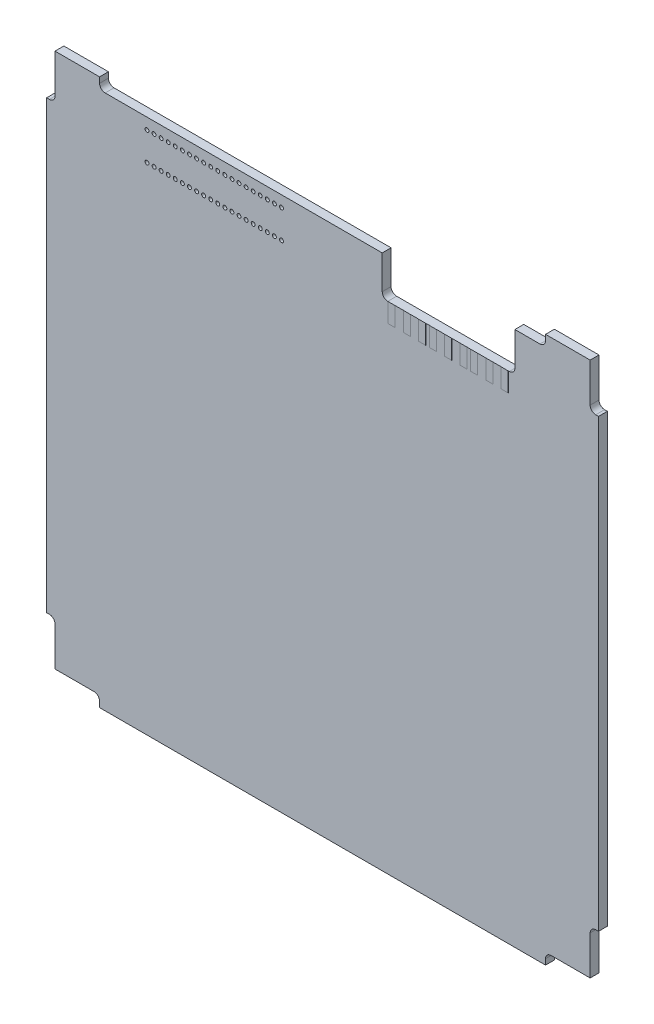
SolidWorks part; units mm, degrees
material "ABS"
ref_plane "Front Plane" through (0, 0, 0) normal (0, 0, 1) x (1, 0, 0)
ref_plane "Top Plane" through (0, 0, 0) normal (0, 1, 0) x (1, 0, 0)
ref_plane "Right Plane" through (0, 0, 0) normal (1, 0, 0) x (0, 0, -1)
sketch "Sketch1" plane through (0, 0, 0) normal (0, 0, 1) x (1, 0, 0)
  line L0 (-40, 50) -> (-40, 48)
  line L1 (-50, -50) -> (50, -50)
  line L2 (-50, -50) -> (-50, 50)
  line L3 (-50, 50) -> (50, 50)
  line L4 (50, -50) -> (50, 50)
  line L5 (-50, -50) -> (50, 50) construction
  line L6 (-50, 50) -> (50, -50) construction
  line L7 (-50, 50) -> (-40, 50)
  line L8 (-50, 50) -> (-50, 40)
  line L9 (-40, 48) -> (-48, 48)
  line L10 (-48, 48) -> (-48, 40)
  line L11 (50, 50) -> (40, 50)
  line L12 (50, 50) -> (50, 40)
  line L13 (-48, 40) -> (-50, 40)
  line L14 (50, 40) -> (48, 40)
  line L15 (-50, -50) -> (-37.8649, -50)
  line L16 (-50, -50) -> (-50, -37.8649)
  line L17 (50, 50) -> (50, 40)
  line L18 (50, 50) -> (40, 50)
  line L19 (50, -50) -> (41.5, -50)
  line L20 (50, -50) -> (50, -41.5)
  line L21 (48, 40) -> (48, 48)
  line L22 (48, 48) -> (40, 48)
  line L23 (40, 48) -> (40, 50)
  line L24 (40, -50) -> (40, -48)
  line L25 (50, -50) -> (40, -50)
  line L26 (50, -50) -> (50, -40)
  line L27 (40, -48) -> (48, -48)
  line L28 (48, -48) -> (48, -40)
  line L29 (48, -40) -> (50, -40)
  line L30 (-50, -40) -> (-48, -40)
  line L31 (-50, -50) -> (-50, -40)
  line L32 (-50, -50) -> (-40, -50)
  line L33 (-48, -40) -> (-48, -48)
  line L34 (-48, -48) -> (-40, -48)
  line L35 (-40, -48) -> (-40, -50)
  point P0 (0, 0)
  point P38 (0, 0)
  dimension "D1" = 100
  dimension "D2" = 100
  dimension "D3" = 2
  dimension "D4" = 10
  dimension "D5" = 4
extrude "Boss-Extrude1" add sketch "Sketch1" along normal blind 1.5875 contours L1 L4 L3 L2 region at (0, 0, 0)
sketch "Sketch2" plane through (0, 0, 1.5875) normal (0, 0, 1) x (1, 0, 0)
  line L0 (0, 50) -> (0, -50) construction
  line L1 (-40, 50) -> (40, 50) construction
  line L2 (-40, -50) -> (40, -50) construction
  line L3 (-50, -40) -> (-50, 40) construction
  line L4 (-40, 50) -> (40, 50) construction
  circle A0 centre (-31.5, 44) radius 0.35
  circle A1 centre (-30.23, 44) radius 0.35
  circle A2 centre (-28.96, 44) radius 0.35
  circle A3 centre (-27.69, 44) radius 0.35
  circle A4 centre (-26.42, 44) radius 0.35
  circle A5 centre (-25.15, 44) radius 0.35
  circle A6 centre (-23.88, 44) radius 0.35
  circle A7 centre (-22.61, 44) radius 0.35
  circle A8 centre (-21.34, 44) radius 0.35
  circle A9 centre (-20.07, 44) radius 0.35
  circle A10 centre (-18.8, 44) radius 0.35
  circle A11 centre (-17.53, 44) radius 0.35
  circle A12 centre (-16.26, 44) radius 0.35
  circle A13 centre (-14.99, 44) radius 0.35
  circle A14 centre (-13.72, 44) radius 0.35
  circle A15 centre (-12.45, 44) radius 0.35
  circle A16 centre (-11.18, 44) radius 0.35
  circle A17 centre (-9.91, 44) radius 0.35
  circle A18 centre (-8.64, 44) radius 0.35
  circle A19 centre (-7.37, 44) radius 0.35
  circle A20 centre (-30.23, 38.92) radius 0.35
  circle A21 centre (-28.96, 38.92) radius 0.35
  circle A22 centre (-27.69, 38.92) radius 0.35
  circle A23 centre (-26.42, 38.92) radius 0.35
  circle A24 centre (-25.15, 38.92) radius 0.35
  circle A25 centre (-23.88, 38.92) radius 0.35
  circle A26 centre (-22.61, 38.92) radius 0.35
  circle A27 centre (-21.34, 38.92) radius 0.35
  circle A28 centre (-20.07, 38.92) radius 0.35
  circle A29 centre (-18.8, 38.92) radius 0.35
  circle A30 centre (-17.53, 38.92) radius 0.35
  circle A31 centre (-16.26, 38.92) radius 0.35
  circle A32 centre (-14.99, 38.92) radius 0.35
  circle A33 centre (-13.72, 38.92) radius 0.35
  circle A34 centre (-12.45, 38.92) radius 0.35
  circle A35 centre (-11.18, 38.92) radius 0.35
  circle A36 centre (-9.91, 38.92) radius 0.35
  circle A37 centre (-8.64, 38.92) radius 0.35
  circle A38 centre (-7.37, 38.92) radius 0.35
  circle A39 centre (-31.5, 38.92) radius 0.35
  dimension "D1" = 0.7
  dimension "D4" = 18.5
  dimension "D5" = 6
  dimension "D2" = 5.08
  dimension "D3" = 1.27
extrude "Cut-Extrude1" cut sketch "Sketch2" against normal through all
sketch "Sketch3" plane through (0, 50, 0) normal (0, 1, 0) x (1, 0, 0)
  line L0 (-40, 0) -> (40, 0) construction
  line L1 (10.7, 0) -> (19.7, 0)
  line L2 (10.7, 0) -> (10.7, -1.5875)
  line L3 (10.7, -1.5875) -> (19.7, -1.5875)
  line L4 (-40, -1.5875) -> (-40, 0) construction
  line L5 (-40, -1.5875) -> (40, -1.5875) construction
  line L6 (15.2, 0) -> (15.2, -1.5875) construction
  line L7 (12, 0) -> (12, -1.5875) construction
  line L8 (18.4, 0) -> (18.4, -1.5875) construction
  line L9 (-40, -1.5875) -> (40, -1.5875) construction
  line L12 (19.7, 0) -> (34.5, 0)
  line L14 (19.7, -1.5875) -> (34.5, -1.5875)
  line L15 (34.5, 0) -> (34.5, -1.5875)
  dimension "D1" = 9
  dimension "D2" = 6.4
  dimension "D3" = 3.2
  dimension "D5" = 14.8
  dimension "D6" = 50.7
extrude "Cut-Extrude2" cut sketch "Sketch3" against normal blind 11.0216
fillet "Fillet2" radius 1 2 edges at (10.7, 38.9784, 0.7938) (34.5, 38.9784, 0.7937)
sketch "Sketch5" plane through (0, 0, 0) normal (0, 0, -1) x (-1, 0, 0)
  line L0 (40, -50) -> (-40, -50) construction
  line L1 (-49.5, 50) -> (49.5, 50)
  line L2 (-49.5, 50) -> (-49.5, -50)
  line L3 (-49.5, -50) -> (49.5, -50)
  line L4 (49.5, 50) -> (49.5, -50)
  line L5 (40, 50) -> (-10.7, 50) construction
  line L6 (50, -40) -> (50, 40) construction
  dimension "D1" = 99
  dimension "D2" = 0.5
extrude "Cut-Extrude3" cut sketch "Sketch5" against normal through all flip side to cut
sketch "Sketch6" plane through (0, 0, 1.5875) normal (0, 0, 1) x (1, 0, 0)
  line L0 (12.4, 38.9784) -> (12.4, 35.5484) construction
  line L1 (11.765, 38.9784) -> (13.035, 38.9784)
  line L2 (11.765, 38.9784) -> (11.765, 35.5484)
  line L3 (11.765, 35.5484) -> (13.035, 35.5484)
  line L4 (13.035, 38.9784) -> (13.035, 35.5484)
  line L5 (14.505, 38.9784) -> (15.775, 38.9784)
  line L6 (14.505, 38.9784) -> (14.505, 35.5484)
  line L7 (14.505, 35.5484) -> (15.775, 35.5484)
  line L8 (15.775, 38.9784) -> (15.775, 35.5484)
  line L9 (17.245, 38.9784) -> (18.515, 38.9784)
  line L10 (17.245, 38.9784) -> (17.245, 35.5484)
  line L11 (17.245, 35.5484) -> (18.515, 35.5484)
  line L12 (18.515, 38.9784) -> (18.515, 35.5484)
  line L13 (15.14, 38.9784) -> (15.14, 35.5484) construction
  line L14 (17.88, 38.9784) -> (17.88, 35.5484) construction
  line L15 (11.7, 38.9784) -> (33.5, 38.9784) construction
  line L16 (12.8, 39.7784) -> (12, 39.7784) construction
  line L17 (19.165, 38.9784) -> (20.435, 38.9784)
  line L18 (19.165, 38.9784) -> (19.165, 35.5484)
  line L19 (19.165, 35.5484) -> (20.435, 35.5484)
  line L20 (20.435, 38.9784) -> (20.435, 35.5484)
  line L21 (21.905, 38.9784) -> (23.175, 38.9784)
  line L22 (21.905, 38.9784) -> (21.905, 35.5484)
  line L23 (21.905, 35.5484) -> (23.175, 35.5484)
  line L24 (23.175, 38.9784) -> (23.175, 35.5484)
  line L25 (24.645, 38.9784) -> (25.915, 38.9784)
  line L26 (24.645, 38.9784) -> (24.645, 35.5484)
  line L27 (24.645, 35.5484) -> (25.915, 35.5484)
  line L28 (25.915, 38.9784) -> (25.915, 35.5484)
  line L29 (19.8, 38.9784) -> (19.8, 35.5484) construction
  line L30 (22.54, 38.9784) -> (22.54, 35.5484) construction
  line L31 (25.28, 38.9784) -> (25.28, 35.5484) construction
  line L32 (26.565, 38.9784) -> (27.835, 38.9784)
  line L33 (26.565, 38.9784) -> (26.565, 35.5484)
  line L34 (26.565, 35.5484) -> (27.835, 35.5484)
  line L35 (27.835, 38.9784) -> (27.835, 35.5484)
  line L36 (29.305, 38.9784) -> (30.575, 38.9784)
  line L37 (29.305, 38.9784) -> (29.305, 35.5484)
  line L38 (29.305, 35.5484) -> (30.575, 35.5484)
  line L39 (30.575, 38.9784) -> (30.575, 35.5484)
  line L40 (32.045, 38.9784) -> (33.315, 38.9784)
  line L41 (32.045, 38.9784) -> (32.045, 35.5484)
  line L42 (32.045, 35.5484) -> (33.315, 35.5484)
  line L43 (33.315, 38.9784) -> (33.315, 35.5484)
  line L44 (27.2, 38.9784) -> (27.2, 35.5484) construction
  line L45 (29.94, 38.9784) -> (29.94, 35.5484) construction
  line L46 (32.68, 38.9784) -> (32.68, 35.5484) construction
  point P20 (12.4, 39.7784)
  point P42 (19.8, 39.7784)
  point P61 (27.2, 39.7784)
  dimension "D1" = 1.27
  dimension "D2" = 3.43
  dimension "D3" = 2.74
  dimension "D4" = 2.74
  dimension "D6" = 7.4
  dimension "D5" = 3
extrude "Boss-Extrude2" add sketch "Sketch6" along normal blind 0.01
sketch "Sketch7" [suppressed] plane through (0, 0, 1.5875) normal (0, 0, 1) x (1, 0, 0)
  line L0 (-40, 50) -> (-36.5, 50)
  line L1 (-40, 50) -> (10.7, 50) construction
  line L2 (-36.5, 50) -> (-36.5, 48)
  line L3 (-36.5, 48) -> (-41.5, 48)
  line L4 (-40, 48) -> (-48, 48) construction
  line L5 (-41.5, 48) -> (-41.5, 41.5)
  line L6 (-41.5, 41.5) -> (-42, 41.5)
  line L7 (-47, 36.5) -> (-47, -36.5)
  line L8 (-40, 50) -> (-49.5, 50)
  line L9 (-49.5, 50) -> (-49.5, -50)
  line L10 (-49.5, -40) -> (-49.5, 40) construction
  line L11 (0, 0) -> (-49.5, 0) construction
  line L12 (-40, -50) -> (-49.5, -50)
  line L13 (-41.5, -41.5) -> (-42, -41.5)
  line L14 (-41.5, -48) -> (-41.5, -41.5)
  line L15 (-36.5, -48) -> (-41.5, -48)
  line L16 (-36.5, -50) -> (-36.5, -48)
  line L17 (-40, -50) -> (-36.5, -50)
  arc A0 (-42, 41.5) -> (-47, 36.5) centre (-42, 36.5) ccw
  arc A1 (-42, -41.5) -> (-47, -36.5) centre (-42, -36.5) cw
  point P25 (-47, 0)
  dimension "D1" = 5
  dimension "D2" = 13
  dimension "D3" = 8
  dimension "D4" = 8.5
  dimension "D5" = 2.5
  dimension "D6" = 5
sketch "Sketch8" plane through (0, 50, 0) normal (0, 1, 0) x (1, 0, 0)
  line L1 (-40, 0) -> (40, 0)
  line L2 (-40, 0) -> (-40, -1.5875)
  line L3 (-40, -1.5875) -> (40, -1.5875)
  line L4 (40, 0) -> (40, -1.5875)
extrude "Cut-Extrude4" cut sketch "Sketch8" against normal blind 4
fillet "Fillet1" radius 1 8 edges at (-48, -40, 0.7937) (-40, -48, 0.7937) (40, -48, 0.7937) (48, -40, 0.7937) (48, 40, 0.7937) (-48, 40, 0.7937) (40, 46, 0.7937) (-40, 46, 0.7937)
sketch "Sketch9" plane through (0, 0, 1.5975) normal (0, 0, 1) x (1, 0, 0)
  line L0 (15.14, 35.5484) -> (15.14, 46.5484) construction
  line L1 (14.505, 35.5484) -> (15.775, 35.5484) construction
  line L2 (22.54, 35.5484) -> (22.54, 46.5484) construction
  line L3 (21.905, 35.5484) -> (23.175, 35.5484) construction
  line L4 (29.94, 35.5484) -> (29.94, 46.5484) construction
  line L5 (29.305, 35.5484) -> (30.575, 35.5484) construction
  dimension "D1" = 11
  dimension "D2" = 11
  dimension "D3" = 11
